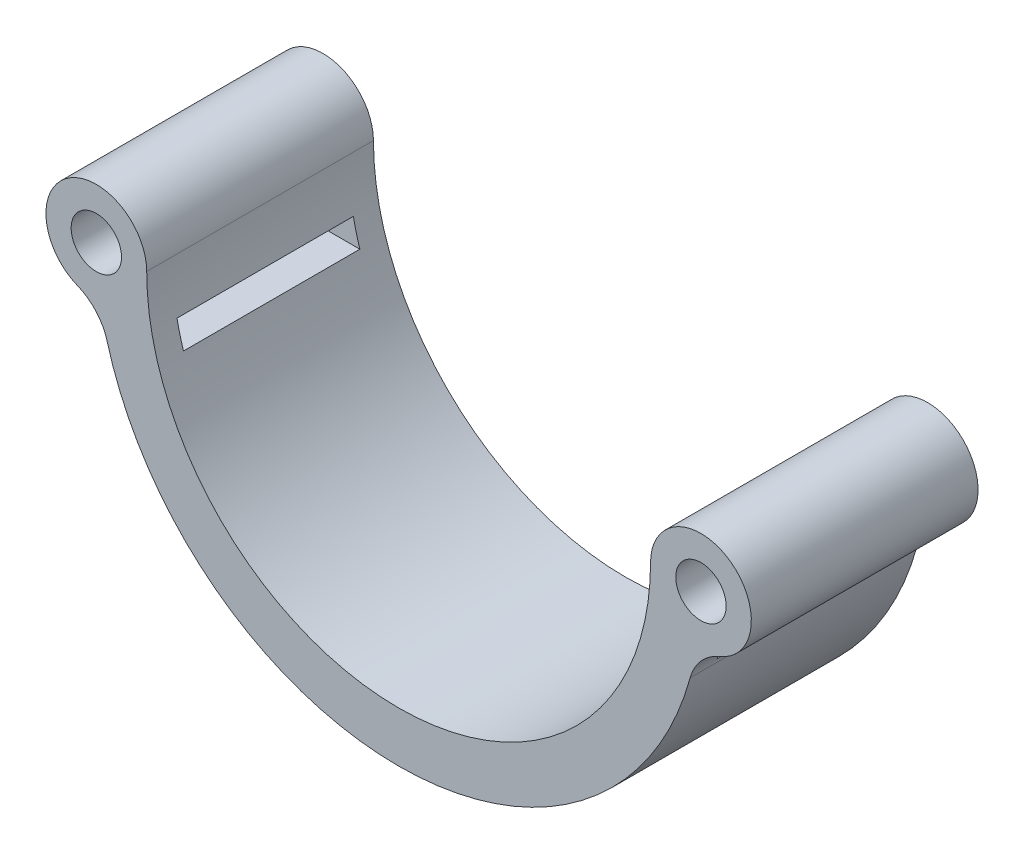
SolidWorks part; units mm, degrees
ref_plane "Front Plane" through (0, 0, 0) normal (0, 0, 1) x (1, 0, 0)
ref_plane "Top Plane" through (0, 0, 0) normal (0, 1, 0) x (1, 0, 0)
ref_plane "Right Plane" through (0, 0, 0) normal (1, 0, 0) x (0, 0, -1)
sketch "Sketch1" plane through (0, 0, 0) normal (0, 0, 1) x (1, 0, 0)
  line L2 (0, 0) -> (0, -69.9797) construction
  arc A3 (50, 0.0269) -> (59.1653, -9.9731) centre (59.9999, -0.008) cw
  arc A4 (50, 0.0269) -> (-50, 0.0269) centre (0, 0) cw
  arc A5 (59.1653, -9.9731) -> (-59.1653, -9.9731) centre (0, 0) cw
  arc A6 (-50, 0.0269) -> (-59.1653, -9.9731) centre (-59.9999, -0.008) ccw
  circle A7 centre (59.9999, -0.008) radius 5
  circle A8 centre (-59.9999, -0.008) radius 5
  dimension "D1" = 10
  dimension "D2" = 50
  dimension "D3" = 10
  dimension "D4" = 10
extrude "Boss-Extrude1" add sketch "Sketch1" along normal blind 45
fillet "Fillet1" radius 10 2 edges at (59.1653, -9.9731, 22.5) (-59.1653, -9.9731, 22.5)
sketch "Sketch3" plane through (0, 0, 0) normal (1, 0, 0) x (0, 0, -1)
  line L0 (0, -9.2787) -> (0, 9.992) construction
  line L1 (-5, -15) -> (-40, -15)
  line L2 (-5, -15) -> (-5, -10)
  line L3 (-5, -10) -> (-40, -10)
  line L4 (-40, -15) -> (-40, -10)
  line L5 (-45, 9.992) -> (-45, -9.2787) construction
  dimension "D1" = 5
  dimension "D2" = 5
  dimension "D3" = 10
  dimension "D4" = 5
extrude "Cut-Extrude1" cut sketch "Sketch3" against normal blind 100 and the other way blind 100
fillet "Fillet2" radius 10 2 edges at (-62.3104, -10, 22.5) (62.3104, -10, 22.5)
ref_plane "Plane1" through (0, 0, 5) normal (0, 0, 1) x (1, 0, 0)
sketch "Sketch4" plane through (0, 0, 5) normal (0, 0, 1) x (1, 0, 0)
  line L0 (40.386, 0) -> (-31.4705, 0) construction
  arc A0 (-49.3934, -16.257) -> (49.5648, -15.7268) centre (0, 0) ccw
  dimension "D1" = 52
